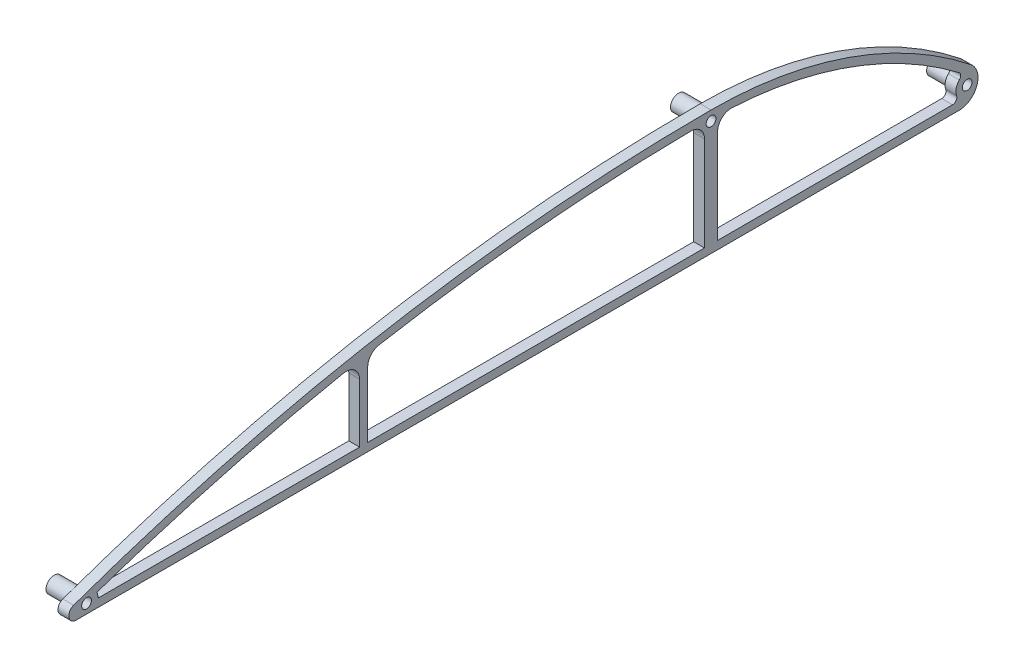
SolidWorks part; units mm, degrees
other "Marquage1"
sketch "Esquisse8" plane through (8, 0, -172.8424) normal (1, 0, 0) x (0, 0, -1)
other "Marquage2"
sketch "Esquisse10" plane through (-6, 20, -172.8424) normal (-0.8365, 0.2588, -0.483) x (-0.5, 0, 0.866)
other "Marquage3"
sketch "Esquisse11" plane through (0, 0, 0) normal (-0.0501, -0.1345, 0.9896) x (0.9942, 0.0873, 0.0622)
ref_plane "Plan de face" through (0, 0, 0) normal (0, 0, 1) x (1, 0, 0)
ref_plane "Plan de dessus" through (0, 0, 0) normal (0, 1, 0) x (1, 0, 0)
ref_plane "Plan de droite" through (0, 0, 0) normal (1, 0, 0) x (0, 0, -1)
sketch "Esquisse2" plane through (0, 0, 0) normal (1, 0, 0) x (0, 0, -1)
  line L0 (0, 0) -> (170.8732, 0)
  arc A1 (173.0499, 6.2408) -> (125, 23) centre (125, -54.2609) ccw
  arc A3 (170.8732, 0) -> (173.0499, 6.2408) centre (170.8732, 3.5) ccw
  arc A4 (125, 23) -> (0, 0) centre (125, -328.1739) ccw
  point P10 (180, 0)
  dimension "D1" = 180
  dimension "D2" = 3.5
  dimension "D3" = 23
  dimension "D4" = 55
extrude "Boss.-Extru.1" add sketch "Esquisse2" along normal blind 2
sketch "Esquisse4" plane through (2, 0, 0) normal (1, 0, 0) x (0, 0, -1)
  line L0 (9.5, 0) -> (9.5, 3.4627) construction
  line L1 (0, 0) -> (9.5, 1.7314) construction
  line L10 (174.369, 3.3283) -> (172.369, 3.3283) construction
  line L11 (0, 0) -> (170.8732, 0) construction
  circle A6 centre (125, 21.2) radius 0.9
  circle A12 centre (172.369, 3.3283) radius 0.9
  arc A13 (170.8732, 0) -> (173.0499, 6.2408) centre (170.8732, 3.5) ccw construction
  circle A15 centre (9.5, 1.7314) radius 0.9
  arc A16 (125, 23) -> (0, 0) centre (125, -328.1739) ccw construction
  dimension "D1" = 1.8
  dimension "D2" = 1.8
  dimension "D7" = 1.8
  dimension "D3" = 1.8
  dimension "D4" = 9.5
  dimension "D6" = 2
extrude "Enlèv. mat.-Extru.2" cut sketch "Esquisse4" against normal through all
sketch "Esquisse9" plane through (0, 0, 0) normal (1, 0, 0) x (0, 0, -1)
  line L26 (126.214, 1.5) -> (171.3359, 1.5)
  line L35 (8.4369, 1.5) -> (170.8732, 1.5)
  line L36 (11.5872, 1.5) -> (60, 1.5)
  line L40 (61.5, 1.5) -> (123.786, 1.5)
  line L42 (60, 1.5) -> (60, 15.4055)
  line L44 (61.5, 1.5) -> (61.5, 15.6859)
  line L45 (123.786, 21.4979) -> (123.786, 1.5)
  line L46 (126.214, 21.4979) -> (126.214, 1.5)
  arc A20 (60, 15.4055) -> (11.4359, 2.5451) centre (125, -328.1739) ccw
  circle A21 centre (125, 21.2) radius 0.9 construction
  circle A22 centre (9.5, 1.7314) radius 0.9 construction
  arc A23 (173.0499, 6.2408) -> (125, 23) centre (125, -54.2609) ccw construction
  arc A25 (171.778, 5.3435) -> (171.3359, 1.5) centre (172.369, 3.3283) ccw
  circle A26 centre (172.369, 3.3283) radius 0.9 construction
  arc A35 (170.8732, 1.5) -> (172.117, 5.0662) centre (170.8732, 3.5) ccw
  arc A39 (172.117, 5.0662) -> (125, 21.5) centre (125, -54.2609) ccw
  arc A40 (125, 21.5) -> (8.4369, 1.5) centre (125, -328.1739) ccw
  arc A42 (171.778, 5.3435) -> (126.214, 21.4979) centre (125, -54.2609) ccw
  arc A43 (123.786, 21.4979) -> (61.5, 15.6859) centre (125, -328.1739) ccw
  arc A54 (11.5872, 1.5) -> (11.4359, 2.5451) centre (9.5, 1.7314) ccw
  dimension "D1" = 1.5
  dimension "D2" = 1.25
  dimension "D3" = 1.2
  dimension "D5" = 1.25
  dimension "D4" = 1.2
  dimension "D6" = 1.5
  dimension "D7" = 60
extrude "Enlèv. mat.-Extru.3" cut sketch "Esquisse9" along normal blind 4
fillet "Congé2" radius 1.35 1 edges at (1, 0, 0)
fillet "Congé3" radius 2.5 4 edges at (1, 21.4979, -126.214) (1, 21.4979, -123.786) (1, 15.4055, -60) (1, 15.6859, -61.5)
fillet "Congé4" radius 0.8 2 edges at (1, 1.5, -171.3359) (1, 5.3435, -171.778)
sketch "Esquisse12" plane through (2, 0, 0) normal (1, 0, 0) x (0, 0, -1)
  line L0 (125, 21.2) -> (123.5016, 20.1382)
  line L1 (125, 21.2) -> (126.5346, 20.1382)
  line L2 (9.5, 1.7314) -> (6.3294, -0.4887)
  line L3 (9.5, 1.7314) -> (12.6706, -0.4887)
  line L4 (172.369, 3.3283) -> (170.18, 1.7956)
  line L5 (172.369, 3.3283) -> (174.5579, 1.7956)
  arc A0 (125.7401, 20.6879) -> (124.2657, 20.6797) centre (125, 21.2) ccw
  circle A1 centre (125, 21.2) radius 0.9 construction
  arc A2 (126.2335, 20.3465) -> (123.7761, 20.3328) centre (125, 21.2) ccw
  arc A3 (123.786, 18.9801) -> (121.2593, 21.48) centre (121.286, 18.9801) ccw construction
  arc A4 (128.8407, 21.4102) -> (126.214, 18.9134) centre (128.714, 18.9134) ccw construction
  arc A5 (10.2372, 1.2151) -> (8.7628, 1.2151) centre (9.5, 1.7314) ccw
  circle A6 centre (9.5, 1.7314) radius 0.9 construction
  arc A7 (10.7287, 0.871) -> (8.2713, 0.871) centre (9.5, 1.7314) ccw
  arc A8 (173.5977, 2.468) -> (171.1402, 2.468) centre (172.369, 3.3283) ccw
  arc A9 (173.1062, 2.8121) -> (171.6317, 2.8121) centre (172.369, 3.3283) ccw
  circle A10 centre (172.369, 3.3283) radius 0.9 construction
  circle M5 centre (172.369, 3.3283) radius 0.9
  circle M6 centre (125, 21.2) radius 0.9
  circle M7 centre (9.5, 1.7314) radius 0.9
  dimension "D1" = 3
  dimension "D3" = 3
  dimension "D5" = 3
  dimension "D2" = 110
  dimension "D4" = 110
  dimension "D6" = 110
extrude "Boss.-Extru.2" add sketch "Esquisse12" against normal blind 6 contours L5 A8 L4 M5 | L1 A2 L0 M6 | L3 A7 L2 M7 region at (2, 20.5374, -123.9988) region at (2, 1.0743, -8.4951) region at (2, 2.6713, -171.3641)
